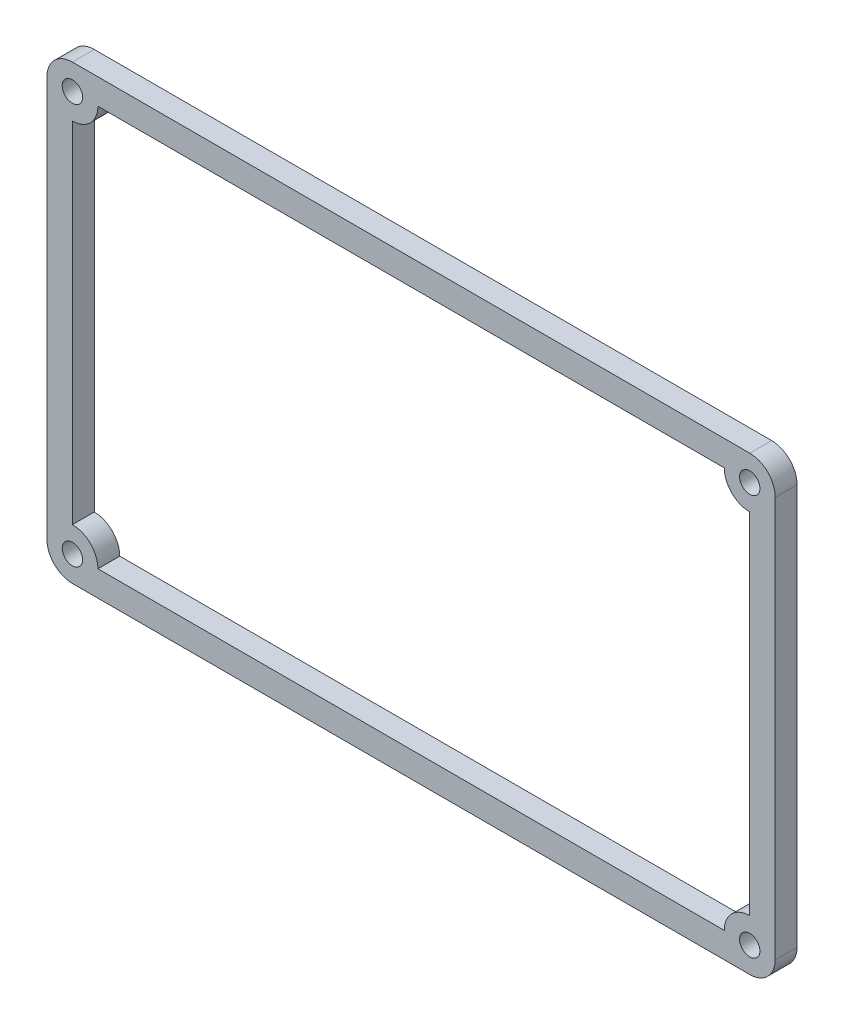
SolidWorks part; units mm, degrees
ref_plane "Front Plane" through (0, 0, 0) normal (0, 0, 1) x (1, 0, 0)
ref_plane "Top Plane" through (0, 0, 0) normal (0, 1, 0) x (1, 0, 0)
ref_plane "Right Plane" through (0, 0, 0) normal (1, 0, 0) x (0, 0, -1)
sketch "Sketch1" plane through (0, 0, 0) normal (0, 0, 1) x (1, 0, 0)
  line L1 (-46.5, -31) -> (46.5, -31)
  line L2 (-50, -27.5) -> (-50, 27.5)
  line L3 (-46.5, 31) -> (46.5, 31)
  line L4 (50, -27.5) -> (50, 27.5)
  line L5 (-50, -31) -> (50, 31) construction
  line L6 (-50, 31) -> (50, -31) construction
  circle A0 centre (-46.5, 27.5) radius 1.4
  circle A1 centre (46.5, 27.5) radius 1.4
  circle A2 centre (46.5, -27.5) radius 1.4
  circle A3 centre (-46.5, -27.5) radius 1.4
  arc A4 (-46.5, -31) -> (-50, -27.5) centre (-46.5, -27.5) cw
  arc A5 (46.5, -31) -> (50, -27.5) centre (46.5, -27.5) ccw
  arc A6 (46.5, 31) -> (50, 27.5) centre (46.5, 27.5) cw
  arc A7 (-50, 27.5) -> (-46.5, 31) centre (-46.5, 27.5) cw
  point P14 (0, 0)
  dimension "D1" = 2.8
  dimension "D8" = 3.5
  dimension "D2" = 46.5
  dimension "D3" = 46.5
  dimension "D4" = 27.5
  dimension "D5" = 27.5
  dimension "D6" = 100
  dimension "D7" = 62
extrude "Boss-Extrude1" add sketch "Sketch1" along normal blind 3
sketch "Sketch2" plane through (0, 0, 3) normal (0, 0, 1) x (1, 0, 0)
  line L0 (46.5, 31) -> (-46.5, 31) construction
  line L1 (-43, -27.5) -> (43, -27.5)
  line L2 (-43, -27.5) -> (-43, 27.5)
  line L3 (-43, 27.5) -> (43, 27.5)
  line L4 (43, -27.5) -> (43, 27.5)
  line L5 (-43, -27.5) -> (43, 27.5) construction
  line L6 (-43, 27.5) -> (43, -27.5) construction
  line L7 (-46.5, -24) -> (46.5, -24)
  line L8 (-46.5, -24) -> (-46.5, 24)
  line L9 (-46.5, 24) -> (46.5, 24)
  line L10 (46.5, -24) -> (46.5, 24)
  line L11 (-46.5, -24) -> (46.5, 24) construction
  line L12 (-46.5, 24) -> (46.5, -24) construction
  line L13 (50, -27.5) -> (50, 27.5) construction
  point P0 (0, 0)
  point P6 (0, 0)
  dimension "D1" = 3.5
  dimension "D2" = 3.5
  dimension "D3" = 7
  dimension "D4" = 7
extrude "Cut-Extrude1" cut sketch "Sketch2" against normal blind 3 contours L9 L8 L7 L2 | L9 L2 L7 L4 | L2 L9 L4 L3 | L7 L10 L9 L4 | L7 L2 L1 L4 region at (0, -25.75, 3) region at (-44.75, 0, 3) region at (0, 0, 3) region at (44.75, 0, 3) region at (0, 25.75, 3)
fillet "Fillet1" radius 3.5 4 edges at (-43, -24, 1.5) (43, -24, 1.5) (43, 24, 1.5) (-43, 24, 1.5)
